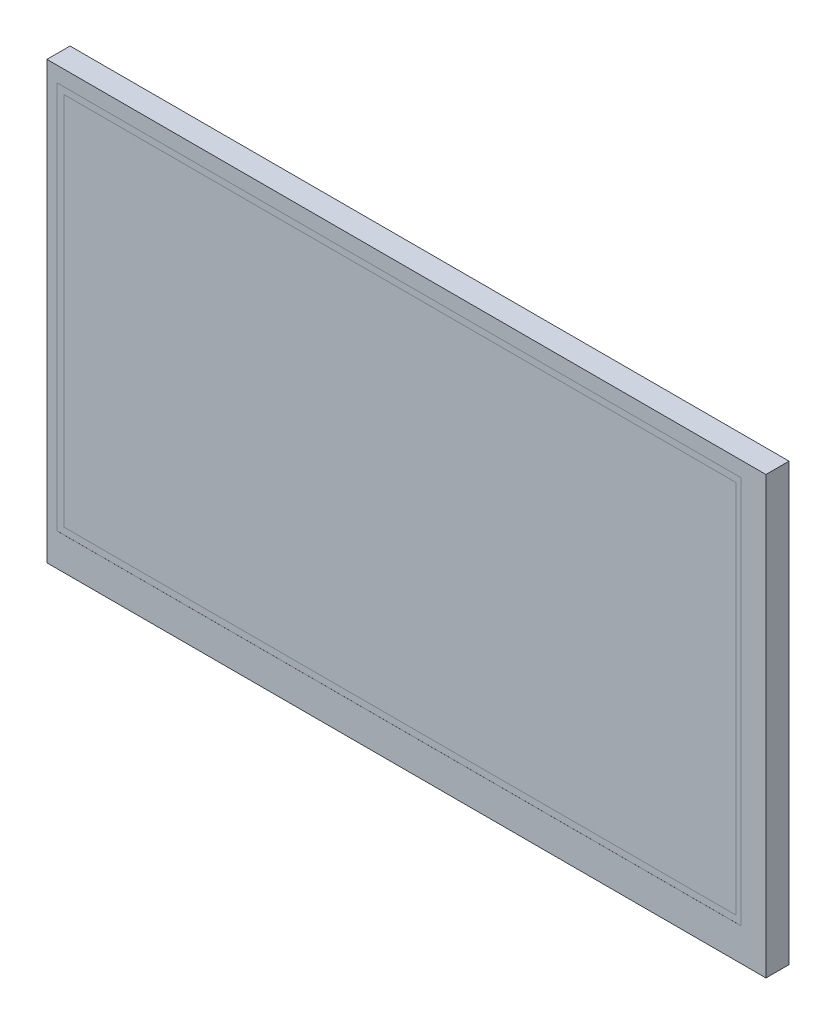
SolidWorks part; units mm, degrees
ref_plane "Front Plane" through (0, 0, 0) normal (0, 0, 1) x (1, 0, 0)
ref_plane "Top Plane" through (0, 0, 0) normal (0, 1, 0) x (1, 0, 0)
ref_plane "Right Plane" through (0, 0, 0) normal (1, 0, 0) x (0, 0, -1)
sketch "Sketch2" plane through (0, 0, 0) normal (0, 0, 1) x (1, 0, 0)
  line L1 (90, -52) -> (-90, -52)
  line L2 (90, -52) -> (90, 52)
  line L3 (90, 52) -> (-90, 52)
  line L4 (-90, -52) -> (-90, 52)
  line L5 (90, -52) -> (-90, 52) construction
  line L6 (90, 52) -> (-90, -52) construction
  point P0 (0, 0)
  dimension "D1" = 104
  dimension "D2" = 180
extrude "PCB" add sketch "Sketch2" along normal blind 1.6
hole_wizard "Ø3.2 (3.2) Diameter Hole1" positions "Sketch4" profile "Sketch3" hole size "Ø3.2" standard "ANSI Metric" end condition through all
sketch "Sketch4" plane through (0, 0, 1.6) normal (0, 0, 1) x (1, 0, 0)
  line L0 (-90, 52) -> (-90, -52) construction
  line L1 (-90, -52) -> (90, -52) construction
  point P4 (-87, 49)
  point P11 (87, 49)
  point P13 (87, -49)
  point P15 (-87, -49)
  dimension "D1" = 3
  dimension "D2" = 98
  dimension "D3" = 3
  dimension "D4" = 174
sketch "Sketch3" plane through (-87, 49, 1.6) normal (1, 0, 0) x (0, -1, 0)
  line L0 (0, 0) -> (0, 1.6)
  line L1 (0, 1.6) -> (1.6, 1.6)
  line L2 (1.6, 1.6) -> (1.6, 0)
  line L5 (1.6, 0) -> (0, 0)
  line L11 (0, -6.35) -> (0, 107.95) construction
  dimension "Thru Hole Dia." = 3.2
  dimension "Thru Hole Depth" = 1.6
sketch "Sketch5" plane through (0, 0, 1.6) normal (0, 0, 1) x (1, 0, 0)
  line L0 (-90, 52) -> (-90, -52) construction
  line L1 (82.45, -50) -> (-82.45, -50)
  line L2 (82.45, -50) -> (82.45, 50)
  line L3 (82.45, 50) -> (-82.45, 50)
  line L4 (-82.45, -50) -> (-82.45, 50)
  line L5 (82.45, -50) -> (-82.45, 50) construction
  line L6 (82.45, 50) -> (-82.45, -50) construction
  line L7 (-90, -52) -> (90, -52) construction
  point P0 (0, 0)
  point P5 (-90, 0)
  dimension "D1" = 164.9
  dimension "D2" = 100
  dimension "D3" = 7.55
  dimension "D4" = 2
extrude "Bezel" add sketch "Sketch5" along normal blind 3.7
sketch "Sketch6" plane through (0, 0, 5.3) normal (0, 0, 1) x (1, 0, 0)
  line L0 (-90, 52) -> (-90, -52) construction
  line L1 (76.75, -42.5) -> (-80.15, -42.5)
  line L2 (76.75, -42.5) -> (76.75, 46.5)
  line L3 (76.75, 46.5) -> (-80.15, 46.5)
  line L4 (-80.15, -42.5) -> (-80.15, 46.5)
  line L5 (76.75, -42.5) -> (-80.15, 46.5) construction
  line L6 (76.75, 46.5) -> (-80.15, -42.5) construction
  line L7 (-90, -52) -> (90, -52) construction
  point P0 (-1.7, 2)
  dimension "D1" = 156.9
  dimension "D2" = 89
  dimension "D3" = 9.85
  dimension "D4" = 9.5
extrude "Visual Area (VA)" cut sketch "Sketch6" against normal blind 0.01
sketch "Sketch7" plane through (0, 0, 5.29) normal (0, 0, 1) x (1, 0, 0)
  line L0 (-90, -52) -> (90, -52) construction
  line L1 (75.55, -40.96) -> (-78.53, -40.96)
  line L2 (75.55, -40.96) -> (75.55, 44.96)
  line L3 (75.55, 44.96) -> (-78.53, 44.96)
  line L4 (-78.53, -40.96) -> (-78.53, 44.96)
  line L5 (75.55, -40.96) -> (-78.53, 44.96) construction
  line L6 (75.55, 44.96) -> (-78.53, -40.96) construction
  line L7 (-90, 52) -> (-90, -52) construction
  point P0 (-1.49, 2)
  dimension "D1" = 154.08
  dimension "D2" = 85.92
  dimension "D3" = 11.04
  dimension "D4" = 11.47
split line "LCD Active Area (AA)"
sketch "Sketch8" plane through (0, 0, 1.6) normal (0, 0, 1) x (1, 0, 0)
  circle A0 centre (-87, 49) radius 2.5
  circle A1 centre (87, 49) radius 2.5
  circle A2 centre (87, -49) radius 2.5
  circle A4 centre (-87, -49) radius 2.5
  circle A5 centre (87, -49) radius 1.6 construction
  dimension "D1" = 5
split line "Mounting Hole Pads"
hole_wizard "Ø1.0 (1) Diameter Hole1" positions "Sketch11" profile "Sketch10" hole size "Ø1.0" standard "ANSI Metric" end condition through all
sketch "Sketch11" plane through (0, 0, 1.6) normal (0, 0, 1) x (1, 0, 0)
  line L0 (-90, -52) -> (90, -52) construction
  line L1 (90, -52) -> (90, 52) construction
  point P0 (88.5, -41.91)
  point P18 (85.96, -41.91)
  point P19 (85.96, -39.37)
  point P20 (85.96, -36.83)
  point P21 (85.96, -34.29)
  point P22 (88.5, -39.37)
  point P23 (88.5, -36.83)
  point P24 (88.5, -34.29)
  point P25 (88.5, -24.13)
  point P33 (85.96, -24.13)
  point P34 (85.96, -21.59)
  point P35 (85.96, -19.05)
  point P36 (85.96, -16.51)
  point P37 (85.96, -13.97)
  point P38 (85.96, -11.43)
  point P39 (85.96, -8.89)
  point P40 (85.96, -6.35)
  point P41 (85.96, -3.81)
  point P42 (85.96, -1.27)
  point P43 (85.96, 1.27)
  point P44 (85.96, 3.81)
  point P45 (85.96, 6.35)
  point P46 (85.96, 8.89)
  point P47 (85.96, 11.43)
  point P48 (85.96, 13.97)
  point P49 (85.96, 16.51)
  point P50 (85.96, 19.05)
  point P51 (85.96, 21.59)
  point P52 (85.96, 24.13)
  point P53 (88.5, -21.59)
  point P54 (88.5, -19.05)
  point P55 (88.5, -16.51)
  point P56 (88.5, -13.97)
  point P57 (88.5, -11.43)
  point P58 (88.5, -8.89)
  point P59 (88.5, -6.35)
  point P60 (88.5, -3.81)
  point P61 (88.5, -1.27)
  point P62 (88.5, 1.27)
  point P63 (88.5, 3.81)
  point P64 (88.5, 6.35)
  point P65 (88.5, 8.89)
  point P66 (88.5, 11.43)
  point P67 (88.5, 13.97)
  point P68 (88.5, 16.51)
  point P69 (88.5, 19.05)
  point P70 (88.5, 21.59)
  point P71 (88.5, 24.13)
  point P75 (88.5, 34.29)
  point P83 (85.96, 34.29)
  point P84 (85.96, 36.83)
  point P85 (85.96, 39.37)
  point P86 (85.96, 41.91)
  point P87 (88.5, 36.83)
  point P88 (88.5, 39.37)
  point P89 (88.5, 41.91)
  dimension "D1" = 10.09
  dimension "D2" = 1.5
  dimension "D5" = 7.62
  dimension "D6" = 2.54
  dimension "D7" = 2.54
  dimension "D8" = 10.16
  dimension "D11" = 48.26
  dimension "D12" = 10.16
  dimension "D3" = 2
  dimension "D4" = 4
  dimension "D9" = 2
  dimension "D10" = 20
  dimension "D13" = 2
  dimension "D14" = 4
sketch "Sketch10" plane through (88.5, -41.91, 1.6) normal (1, 0, 0) x (0, -1, 0)
  line L0 (0, 0) -> (0, 1.6)
  line L1 (0, 1.6) -> (0.5, 1.6)
  line L2 (0.5, 1.6) -> (0.5, 0)
  line L5 (0.5, 0) -> (0, 0)
  line L11 (0, -6.35) -> (0, 107.95) construction
  dimension "Thru Hole Dia." = 1
  dimension "Thru Hole Depth" = 1.6
sketch "Sketch12" plane through (0, 0, 5.3) normal (0, 0, 1) x (1, 0, 0)
  line L4 (-82.45, 50) -> (-82.45, -50)
  line L5 (-82.45, -50) -> (82.45, -50)
  line L6 (82.45, -50) -> (82.45, 50)
  line L7 (82.45, 50) -> (-82.45, 50)
  line L8 (-82.45, 50) -> (-82.45, -50)
  line L9 (-82.45, -50) -> (82.45, -50)
  line L10 (82.45, -50) -> (82.45, 50)
  line L11 (82.45, 50) -> (-82.45, 50)
  line L12 (-90, 52) -> (-90, -52)
  line L13 (-90, -52) -> (90, -52)
  line L14 (90, -52) -> (90, 52)
  line L15 (90, 52) -> (-90, 52)
  line L16 (-90, 52) -> (-90, -52)
  line L17 (-90, -52) -> (90, -52)
  line L18 (90, -52) -> (90, 52)
  line L19 (90, 52) -> (-90, 52)
  dimension "D1" = 0
  dimension "D2" = 0
extrude "Cut-Extrude1" cut sketch "Sketch12" against normal through all
ref_plane "AA Vert C/L" through (-1.49, 0, 0) normal (-1, 0, 0) x (0, 0, 1)
ref_plane "AA Horiz C/L" through (0, 2, 0) normal (0, 1, 0) x (1, 0, 0)
